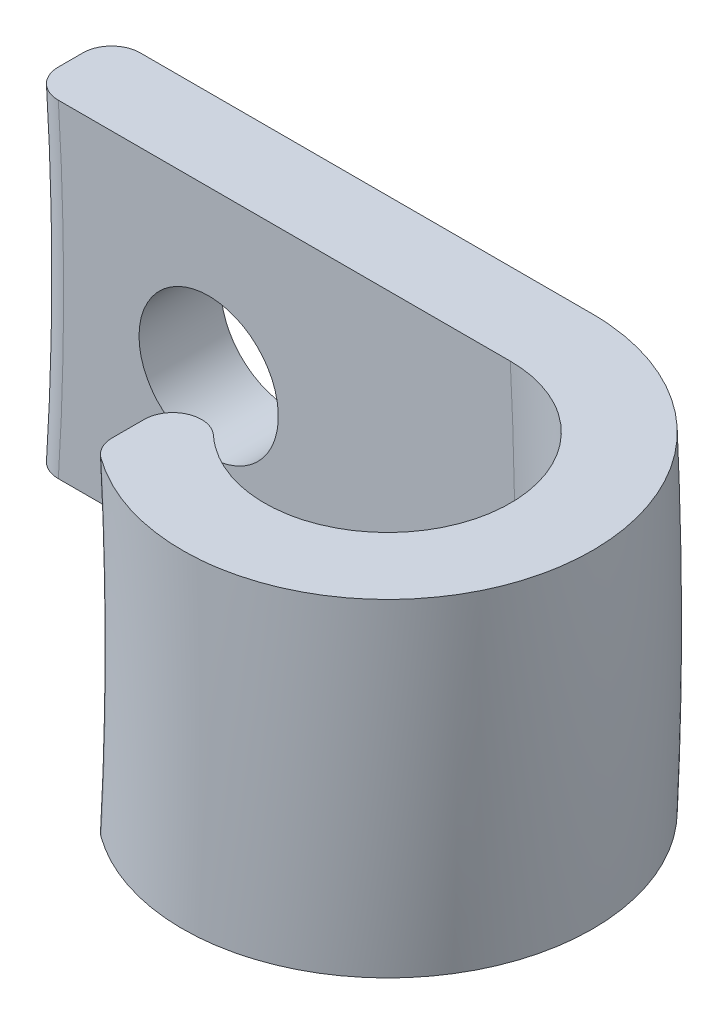
SolidWorks part; units mm, degrees
ref_plane "Plan de face" through (0, 0, 0) normal (0, 0, 1) x (1, 0, 0)
ref_plane "Plan de dessus" through (0, 0, 0) normal (0, 1, 0) x (1, 0, 0)
ref_plane "Plan de droite" through (0, 0, 0) normal (1, 0, 0) x (0, 0, -1)
sketch "Esquisse1" plane through (0, 0, 0) normal (0, 1, 0) x (1, 0, 0)
  line L0 (73.2298, 0) -> (62.22, 0)
  line L1 (70, -5) -> (61.52, -5) construction
  line L2 (70, -8.4771) -> (70, -7.7)
  line L3 (70.7, -7) -> (70, -7) construction
  line L4 (61.52, -1.3) -> (61.52, -0.7)
  line L5 (62.22, -2) -> (73.2298, -2)
  line L7 (0, 0) -> (0, -8.4771) construction
  arc A0 (73.2298, 0) -> (70.2882, -9.0431) centre (73.2298, -5) cw
  arc A1 (71.1786, -7.1892) -> (73.2298, -2) centre (73.2298, -5) ccw
  arc A2 (70, -7.7) -> (71.1786, -7.1892) centre (70.7, -7.7) cw
  arc A3 (70.2882, -9.0431) -> (70, -8.4771) centre (70.7, -8.4771) cw
  arc A4 (62.22, 0) -> (61.52, -0.7) centre (62.22, -0.7) ccw
  arc A5 (62.22, -2) -> (61.52, -1.3) centre (62.22, -1.3) cw
  point P16 (65.76, -5)
  dimension "D3" = 3
  dimension "D1" = 0.7
  dimension "D6" = 5
  dimension "D5" = 70
  dimension "D2" = 65.76
  dimension "D4" = 2
revolve "Révolution1" add sketch "Esquisse1" angle 3.728 about L7
sketch "Esquisse5" plane through (0, 0, 0) normal (1, 0, 0) x (0, 0, -1)
  line L0 (0, 4) -> (-10, 4)
  line L1 (-10, 4) -> (-10, 5.0865)
  line L2 (-10, 5.0865) -> (0, 5.0865)
  line L3 (0, 5.0865) -> (0, 4)
  line L4 (0, -4) -> (-10, -4)
  line L5 (-10, -4) -> (-10, -5.0865)
  line L6 (-10, -5.0865) -> (0, -5.0865)
  line L7 (0, -5.0865) -> (0, -4)
  line L8 (-10, 4.7614) -> (-10, -4.7614) construction
  line L9 (-0.7, 4) -> (-1.3, 4) construction
  line L10 (-0.7, -4) -> (-1.3, -4) construction
  line L11 (0, -4.0455) -> (0, 4.0455) construction
  line L12 (-10, 4.7614) -> (-10, -4.7614) construction
  ellipse E0 centre (-5, -4.7614) end of major axis (0, -4.7614) minor radius 0.3251 (-9.0431, -4.5701) -> (0, -4.7614) ccw construction
  ellipse E1 centre (-5, 4.7614) end of major axis (0, 4.7614) minor radius 0.3251 (0, 4.7614) -> (-9.0431, 4.5701) ccw construction
extrude "Enlèv. mat.-Extru.3" cut sketch "Esquisse5" along normal through all
hole_wizard "Dégagement M31" positions "Esquisse6" profile "Esquisse7" hole size "M3" standard "DIN" end condition through all
sketch "Esquisse6" plane through (0, 0, 0) normal (0, 0, -1) x (-1, 0, 0)
  line L0 (-62.22, 0) -> (-73.2298, 0) construction
  arc A0 (-62.0913, 4) -> (-62.0913, -4) centre (0, 0) ccw construction
  arc A1 (-73.1205, 4) -> (-73.1205, -4) centre (0, 0) ccw construction
  point P0 (-65.76, 0)
  dimension "D1" = 65.76
sketch "Esquisse7" plane through (65.76, 0, 0) normal (1, 0, 0) x (0, 1, 0)
  line L0 (0, 0) -> (0, 10)
  line L1 (0, 10) -> (1.7, 10)
  line L2 (1.7, 10) -> (1.7, 0)
  line L5 (1.7, 0) -> (0, 0)
  line L11 (0, -6.35) -> (0, 107.95) construction
  dimension "Diamètre du perçage jusqu'au prochain" = 3.4
  dimension "Profondeur du perçage jusqu'au prochain" = 10
equation "\"r\"= 0.7mm"
equation "\"e\"= 2mm"
equation "\"D1@Esquisse1\"=\"r\""
equation "\"rext\"= 70mm"
equation "\"rmiddle\"= 65.76mm"
equation "\"rint\"= 2 * \"rmiddle\" - \"rext\""
equation "\"D5@Esquisse1\"=\"rext\""
equation "\"D2@Esquisse1\"=\"rmiddle\""
equation "\"D4@Esquisse1\"=\"e\""
equation "\"L\"= 8mm"
equation "\"gamma\"= arccos ( 1 - ( ( \"L\" * \"L\" ) / ( \"rint\" * \"rint\" * 2 ) ) )"
equation "\"D2@Révolution1\"=\"gamma\"/2"
equation "\"D1@Révolution1\"=\"gamma\"/2"
equation "\"D1@Esquisse6\"=\"rmiddle\""
